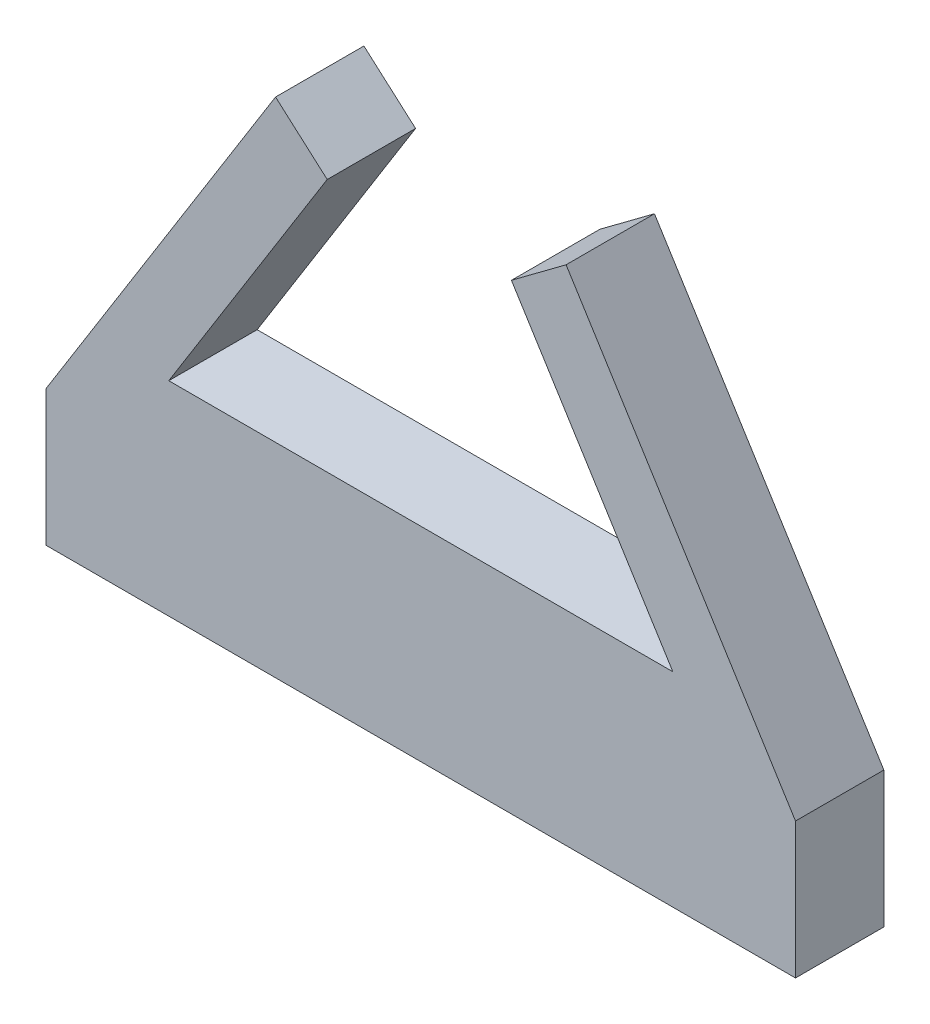
SolidWorks part; units mm, degrees
ref_plane "Front Plane" through (0, 0, 0) normal (0, 0, 1) x (1, 0, 0)
ref_plane "Top Plane" through (0, 0, 0) normal (0, 1, 0) x (1, 0, 0)
ref_plane "Right Plane" through (0, 0, 0) normal (1, 0, 0) x (0, 0, -1)
sketch "Sketch1" plane through (0, 0, 0) normal (0, 0, 1) x (1, 0, 0)
  line L0 (-5, -5) -> (-5, -2) construction
  line L1 (-5, 5) -> (5, 5) construction
  line L2 (-5, 5) -> (-5, -5) construction
  line L3 (-5, -5) -> (5, -5) construction
  line L4 (5, 5) -> (5, -5) construction
  line L5 (-5, 5) -> (5, -5) construction
  line L6 (-5, -5) -> (5, 5) construction
  line L7 (-2.5, 5) -> (2.5, 5) construction
  line L8 (-2.5, 5) -> (-2.5, -5) construction
  line L9 (-2.5, -5) -> (2.5, -5) construction
  line L10 (2.5, 5) -> (2.5, -5) construction
  line L11 (-2.5, 5) -> (2.5, -5) construction
  line L12 (-2.5, -5) -> (2.5, 5) construction
  line L13 (-2.5, 5) -> (2.5, 5) construction
  line L14 (-2.5, 5) -> (-2.5, 2) construction
  line L15 (-2.5, 2) -> (2.5, 2) construction
  line L16 (2.5, 5) -> (2.5, 2) construction
  line L17 (-2.5, 5) -> (2.5, 2) construction
  line L18 (-2.5, 2) -> (2.5, 5) construction
  line L19 (5, -5) -> (5, -2) construction
  line L20 (-5, -2) -> (-2.5, 2)
  line L21 (-2.5, 2) -> (-5, -2)
  line L22 (2.5, 2) -> (5, -2)
  line L23 (-5, -2) -> (-6.875, -5)
  line L24 (5, -2) -> (6.875, -5)
  line L25 (6.875, -5) -> (-6.875, -5)
  line L26 (-2.5, 2) -> (2.5, 2)
  line L27 (-2.5, 2.3) -> (2.6663, 2.3)
  line L28 (2.6663, 2.3) -> (5.2544, -1.841)
  line L29 (5.2544, -1.841) -> (7.4163, -5.3)
  line L30 (7.4163, -5.3) -> (-7.4163, -5.3)
  line L31 (-5.2544, -1.841) -> (-7.4163, -5.3)
  line L32 (-5.2544, -1.841) -> (-2.7544, 2.159)
  line L33 (-3.5584, -2.901) -> (-1.0584, 1.099)
  line L34 (-6.9504, -0.781) -> (-11.0248, -7.3)
  line L35 (11.0248, -7.3) -> (-11.0248, -7.3)
  line L36 (6.9504, -0.781) -> (11.0248, -7.3)
  line L37 (3.7748, 4.3) -> (6.9504, -0.781)
  line L38 (-2.5, 4.3) -> (3.7748, 4.3)
  line L39 (-6.9504, -0.781) -> (-4.2748, 3.5)
  line L40 (-4.2748, 3.5) -> (4.2748, 3.5)
  line L41 (4.2748, 3.5) -> (2.6663, 2.3)
  line L42 (-2.7544, 2.159) -> (-4.2748, 3.5)
  point P0 (0, 0)
  point P6 (0, 0)
  point P13 (0, 3.5)
  dimension "D1" = 10
  dimension "D2" = 10
  dimension "D3" = 5
  dimension "D4" = 3
  dimension "D5" = 3
  dimension "D6" = 3
  dimension "D7" = 0.3
  dimension "D8" = 2
extrude "Boss-Extrude1" add sketch "Sketch1" along normal blind 2.6 contours L32 L42 L39 L34 L35 L36 L37 L41 L28 L29 L30 L31 region at (3.6173, 2.7032, 0)
sketch "Sketch2" plane through (0, -7.3, 0) normal (0, -1, 0) x (1, 0, 0)
  line L1 (-11.0248, 2.6) -> (11.0248, 2.6)
  line L2 (-11.0248, 2.6) -> (-11.0248, 0)
  line L3 (-11.0248, 0) -> (11.0248, 0)
  line L4 (11.0248, 2.6) -> (11.0248, 0)
  line L5 (-11.0248, 2.6) -> (11.0248, 0) construction
  line L6 (-11.0248, 0) -> (11.0248, 2.6) construction
  point P4 (0, 1.3)
extrude "Boss-Extrude2" add sketch "Sketch2" along normal blind 4
